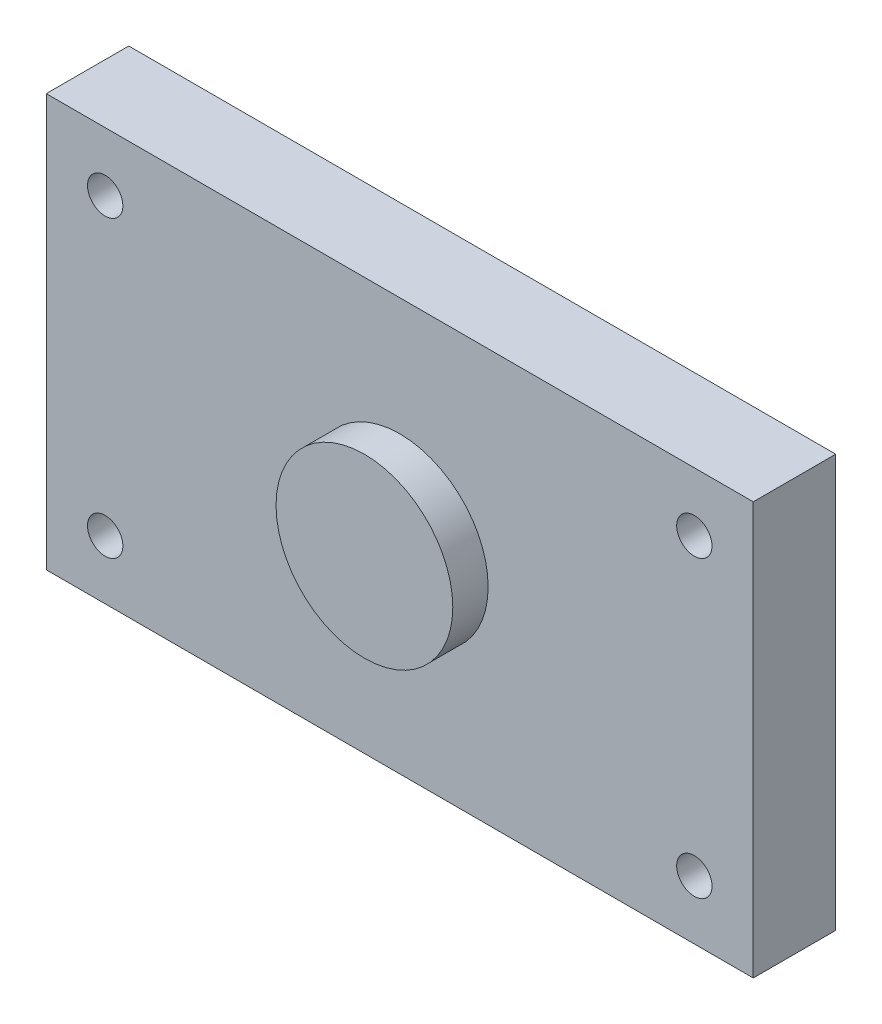
SolidWorks part; units mm, degrees
ref_plane "Front Plane" through (0, 0, 0) normal (0, 0, 1) x (1, 0, 0)
ref_plane "Top Plane" through (0, 0, 0) normal (0, 1, 0) x (1, 0, 0)
ref_plane "Right Plane" through (0, 0, 0) normal (1, 0, 0) x (0, 0, -1)
sketch "Sketch1" plane through (0, 0, 0) normal (0, 0, 1) x (1, 0, 0)
  line L1 (-92.5, 17.5) -> (-32.5, 17.5)
  line L2 (-92.5, 17.5) -> (-92.5, -17.5)
  line L3 (-92.5, -17.5) -> (-32.5, -17.5)
  line L4 (-32.5, 17.5) -> (-32.5, -17.5)
  line L5 (-92.5, 0) -> (-56.7435, 0) construction
  circle A0 centre (-87.5, 12.5) radius 1.5
  circle A1 centre (-87.5, -12.5) radius 1.5
  circle A2 centre (-37.5, 12.5) radius 1.5
  circle A3 centre (-37.5, -12.5) radius 1.5
  circle A4 centre (-62.5, 0) radius 4
  point P4 (0, 0)
  dimension "D2" = 3
  dimension "D5" = 8
  dimension "D6" = 25
  dimension "D7" = 25
  dimension "D8" = 5
  dimension "D9" = 5
  dimension "D10" = 5
  dimension "D1" = 3
  dimension "D3" = 5
  dimension "D4" = 5
  dimension "D11" = 17.5
extrude "Boss-Extrude1" add sketch "Sketch1" along normal blind 7 contours L4 L1 L2 A4 L3 A3 A2 A0 A1 | L5 A4 | A4 L5 region at (-62.5, 1.6977, 0) region at (-62.5, -1.6977, 0) region at (-62.5, 16.8054, 0)
sketch "Sketch2" plane through (-32.5, 0, 0) normal (1, 0, 0) x (0, 0, -1)
  line L1 (0, 25) -> (-7, 25)
  line L2 (0, 25) -> (0, -25)
  line L3 (0, -25) -> (-7, -25)
  line L4 (-7, 25) -> (-7, -25)
  line L6 (-7, 17.5) -> (0, 17.5) construction
  line L7 (-7, -17.5) -> (0, -17.5) construction
  line L8 (-7, 17.5) -> (-7, -17.5) construction
  dimension "D2" = 7.5
  dimension "D3" = 7.5
sketch "Sketch5" plane through (0, 0, 7) normal (0, 0, 1) x (1, 0, 0)
  circle A0 centre (-62.5, 0) radius 7.5
  dimension "D1" = 15
extrude "Boss-Extrude5" add sketch "Sketch5" along normal blind 3
extrude "Cut-Extrude1" cut sketch "Sketch1<3>" along normal blind 3 and the other way blind 3 contours L5 A4 | A4 L5 region at (-62.5, 1.6977, 0) region at (-62.5, -1.6977, 0)
sketch "Sketch1<3>" plane through (0, 0, 0) normal (0, 0, 1) x (1, 0, 0) same geometry as "Sketch1"
